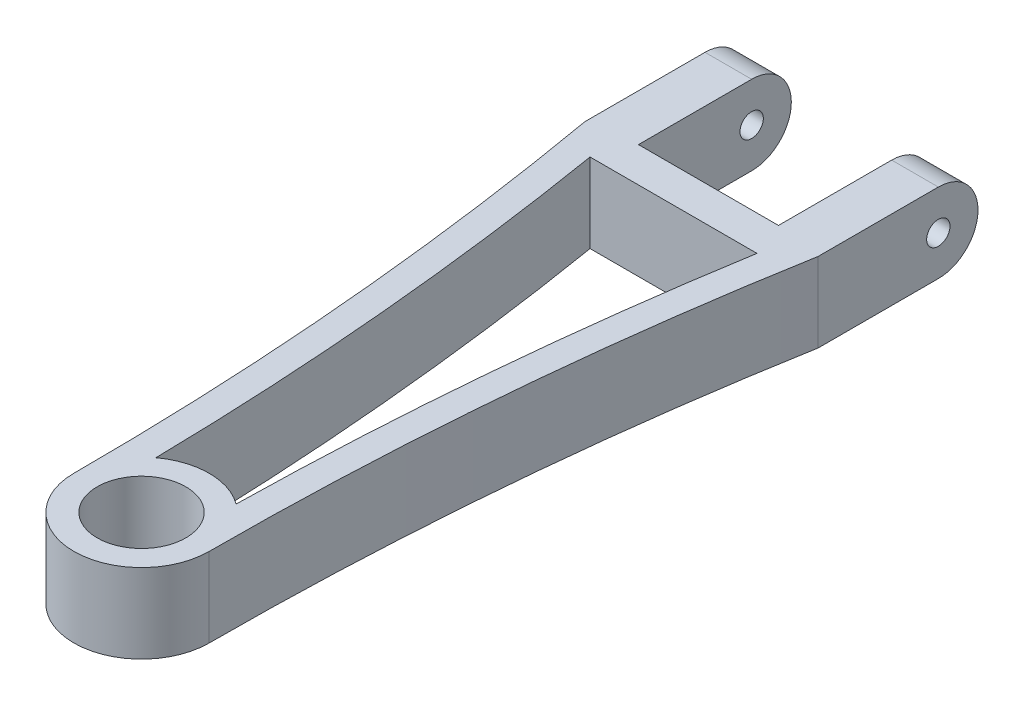
SolidWorks part; units mm, degrees
ref_plane "Front Plane" through (0, 0, 0) normal (0, 0, 1) x (1, 0, 0)
ref_plane "Top Plane" through (0, 0, 0) normal (0, 1, 0) x (1, 0, 0)
ref_plane "Right Plane" through (0, 0, 0) normal (1, 0, 0) x (0, 0, -1)
sketch "Sketch1" plane through (0, 0, 0) normal (0, 1, 0) x (1, 0, 0)
  line L0 (-31.75, 152.4) -> (31.75, 152.4)
  line L1 (0, 0) -> (0, 152.4) construction
  circle A0 centre (0, 0) radius 12.065
  circle A1 centre (0, 0) radius 152.4 construction
  arc A2 (-18.415, 0) -> (18.415, 0) centre (0, 0) ccw
  arc A3 (-31.75, 152.4) -> (-18.415, 0) centre (-895.9396, 0) cw
  arc A4 (31.75, 152.4) -> (18.415, 0) centre (895.9396, 0) ccw
  circle A6 centre (0, 0) radius 18.415 construction
  point P7 (0, 152.4)
  point P14 (18.0975, 0)
  dimension "D1" = 24.13
  dimension "D2" = 152.4
  dimension "D4" = 63.5
  dimension "D3" = 6.35
extrude "Boss-Extrude1" add sketch "Sketch1" along normal mid plane 21.59
sketch "Sketch3" [suppressed] plane through (0, 0, -152.4) normal (0, 0, -1) x (-1, 0, 0)
  line L0 (-1000, 0) -> (49000, 0) construction
  line L1 (0, -15.5111) -> (0, 15.5111) construction
  circle A0 centre (-25.4, 0) radius 3.175
  circle A1 centre (25.4, 0) radius 3.175
  point P6 (0, 0)
  dimension "D1" = 6.35
  dimension "D2" = 25.4
sketch "Sketch4" plane through (0, 0, -152.4) normal (0, 0, -1) x (-1, 0, 0)
  line L0 (0, -23.7718) -> (0, 23.7718) construction
  line L1 (48.961, 0) -> (-48.961, 0) construction
  line L2 (-19.05, 10.795) -> (-19.05, -10.795)
  line L3 (-31.75, 10.795) -> (31.75, 10.795) construction
  line L4 (-31.75, -10.795) -> (31.75, -10.795) construction
  line L6 (-31.75, 10.795) -> (-31.75, -10.795)
  line L7 (-31.75, 10.795) -> (-19.05, 10.795)
  line L8 (-31.75, -10.795) -> (-19.05, -10.795)
  line L9 (31.75, -10.795) -> (19.05, -10.795)
  line L10 (19.05, 10.795) -> (19.05, -10.795)
  line L11 (31.75, 10.795) -> (19.05, 10.795)
  line L12 (31.75, 10.795) -> (31.75, -10.795)
  point P4 (0, 0)
  point P8 (0, 0)
  point P20 (0, 0)
  point P21 (0, 0)
  line M3 (-31.75, -10.795) -> (31.75, -10.795)
  line M4 (31.75, -10.795) -> (31.75, 10.795)
  line M5 (31.75, 10.795) -> (-31.75, 10.795)
  line M6 (-31.75, 10.795) -> (-31.75, -10.795)
  dimension "D1" = 19.05
  dimension "D2" = 12.7
sketch "Sketch5" plane through (0, 0, -152.4) normal (0, 0, -1) x (-1, 0, 0)
  line L0 (-31.75, 10.795) -> (31.75, 10.795) construction
  line L1 (-19.05, -10.795) -> (19.05, -10.795)
  line L2 (-19.05, -10.795) -> (-19.05, 10.795)
  line L3 (-19.05, 10.795) -> (19.05, 10.795)
  line L4 (19.05, -10.795) -> (19.05, 10.795)
  line L5 (-19.05, -10.795) -> (19.05, 10.795) construction
  line L6 (-19.05, 10.795) -> (19.05, -10.795) construction
  line L7 (-31.75, 10.795) -> (-31.75, -10.795) construction
  point P0 (0, 0)
  dimension "D1" = 12.7
extrude "Boss-Extrude2" add sketch "Sketch5" along normal blind 101.6
sketch "Sketch6" plane through (19.05, 0, 0) normal (1, 0, 0) x (0, 0, -1)
  line L0 (152.4, -10.795) -> (154.2889, 10.795)
  line L1 (254, 10.795) -> (152.4, 10.795) construction
  line L2 (152.4, 10.795) -> (152.4, -10.795) construction
  line L3 (154.2889, 10.795) -> (254, 10.795)
  line L4 (254, 10.795) -> (254, -10.795)
  line L5 (254, -10.795) -> (152.4, -10.795)
  line L6 (153.3444, 0) -> (185.0944, 0) construction
  circle A0 centre (185.0944, 0) radius 3.175
  dimension "D3" = 6.35
  dimension "D1" = 5
  dimension "D2" = 31.75
extrude "Cut-Extrude1" cut sketch "Sketch6" against normal up to next
extrude "Boss-Extrude3" add sketch "Sketch4" along normal blind 50.8 contours L10 M5 M3 M4 | L2 M5 M6 M3 region at (25.4, 0, -152.4) region at (-25.4, 0, -152.4)
extrude "Cut-Extrude2" cut sketch "Sketch6<2>" against normal through all both and the other way through all contours A0
sketch "Sketch6<2>" plane through (19.05, 0, 0) normal (1, 0, 0) x (0, 0, -1) same geometry as "Sketch6"
sketch "Sketch7" plane through (31.75, 0, 0) normal (1, 0, 0) x (0, 0, -1)
  line L0 (185.0944, 10.795) -> (203.2, 10.795)
  line L1 (203.2, 10.795) -> (203.2, -10.795)
  line L2 (203.2, -10.795) -> (185.0944, -10.795)
  circle A0 centre (185.0944, 0) radius 10.795
  line M3 (152.4, -10.795) -> (203.2, -10.795)
  line M4 (203.2, -10.795) -> (203.2, 10.795)
  line M5 (203.2, 10.795) -> (152.4, 10.795)
extrude "Cut-Extrude3" cut sketch "Sketch7" against normal through all both and the other way through all contours A0 M3 M4 M5 region at (31.75, 0, -198.0849)
sketch "Sketch8" plane through (0, -10.795, 0) normal (0, -1, 0) x (1, 0, 0)
  line L14 (-22.7159, -144.78) -> (22.7159, -144.78)
  line L15 (-22.7159, -144.78) -> (22.7159, -144.78)
  arc A3 (-10.9192, -14.8285) -> (10.9192, -14.8285) centre (0, 0) ccw
  arc A6 (10.795, 0) -> (22.7159, -144.78) centre (895.9396, 0) ccw
  arc A7 (10.795, 0) -> (-10.795, 0) centre (0, 0) ccw
  arc A8 (-22.7159, -144.78) -> (-10.795, 0) centre (-895.9396, 0) ccw
  arc A9 (10.795, 0) -> (22.7159, -144.78) centre (895.9396, 0) ccw
  arc A10 (10.795, 0) -> (-10.795, 0) centre (0, 0) ccw
  arc A11 (-22.7159, -144.78) -> (-10.795, 0) centre (-895.9396, 0) ccw
  dimension "D1" = 7.62
extrude "Cut-Extrude4" cut sketch "Sketch8" against normal through all both and the other way through all contours A11 L15 A9 A3 region at (0, -10.795, -89.1804)
